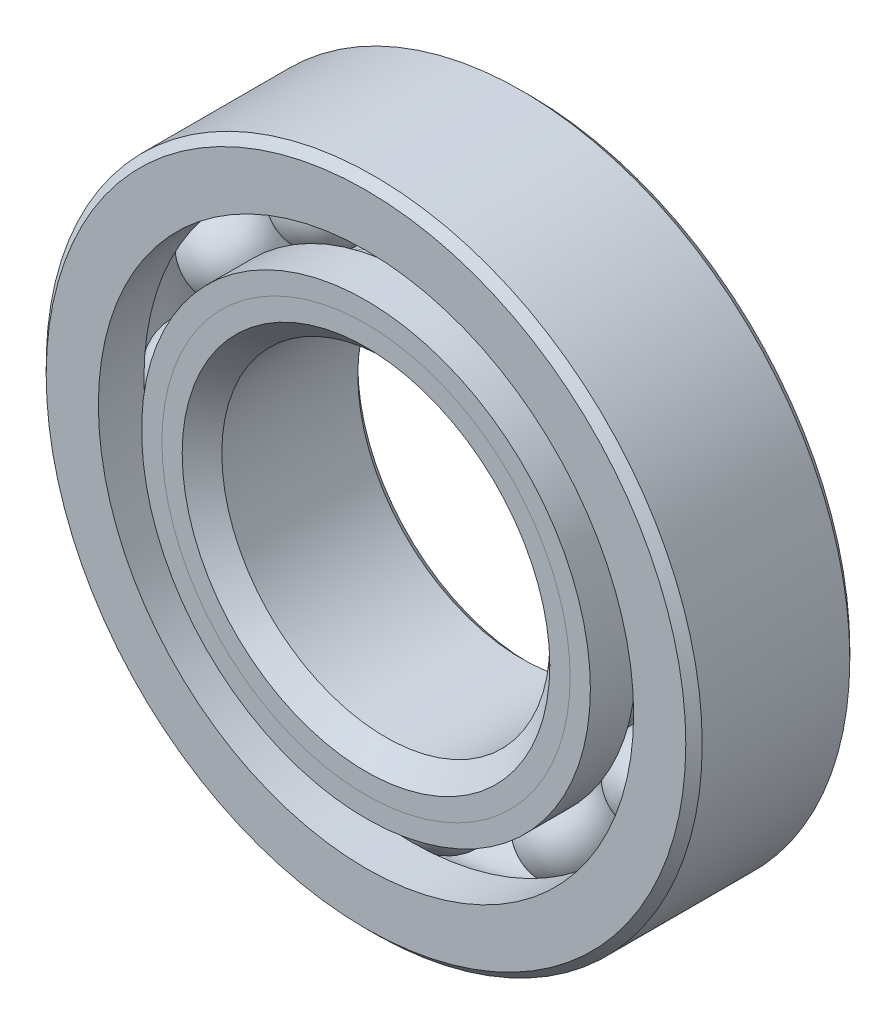
SolidWorks part; units mm, degrees
ref_plane "Front Plane" through (0, 0, 0) normal (0, 0, 1) x (1, 0, 0)
ref_plane "Top Plane" through (0, 0, 0) normal (0, 1, 0) x (1, 0, 0)
ref_plane "Right Plane" through (0, 0, 0) normal (1, 0, 0) x (0, 0, -1)
sketch "Sketch1" plane through (0, 0, 0) normal (1, 0, 0) x (0, 0, -1)
  line L0 (-1.5875, 0) -> (1.5875, 0) construction
  line L1 (0, 6.35) -> (0, -6.35) construction
  line L2 (1.4288, 6.35) -> (-1.4288, 6.35)
  line L3 (-1.4288, 6.35) -> (-1.5875, 6.1913)
  line L4 (-1.5875, 6.1913) -> (-1.5875, 5.1812)
  line L5 (-1.5875, 5.1812) -> (-0.7056, 5.1812)
  line L6 (1.5875, 5.1812) -> (0.7056, 5.1812)
  line L7 (1.5875, 6.1913) -> (1.5875, 5.1812)
  line L8 (1.4288, 6.35) -> (1.5875, 6.1913)
  line L9 (0, 6.35) -> (0, 4.7625) construction
  line L10 (0, 4.7625) -> (0, 3.175) construction
  arc A0 (-0.7056, 5.1812) -> (0.7056, 5.1812) centre (0, 4.7625) cw
  point P14 (0, 3.175)
  dimension "Width" = 3.175
  dimension "OD" = 12.7
  dimension "D1" = 45
  dimension "D2" = 0.1588
  dimension "D3" = 1.4111
  dimension "D4" = 0.4187
revolve "Revolve1" add sketch "Sketch1" angle 360 about L0
sketch "Sketch2" plane through (0, 0, 0) normal (1, 0, 0) x (0, 0, -1)
  line L0 (-1.5875, 4.3438) -> (-0.7056, 4.3438)
  line L1 (-1.5875, 6.1913) -> (-1.5875, -6.1913) construction
  line L2 (-1.5875, 4.3438) -> (-1.5875, 3.9512)
  line L3 (-1.5875, 3.9512) -> (-1.1949, 3.5585)
  line L4 (-1.1949, 3.5585) -> (0, 3.5585)
  line L5 (0, 6.35) -> (0, -6.35) construction
  line L6 (0, 3.5585) -> (0, 3.9421)
  line L7 (0, 3.9421) -> (0, 3.175) construction
  line L8 (-1.5875, 4.3438) -> (-1.5875, 3.5585) construction
  line L9 (-1.5875, 3.5585) -> (-1.1949, 3.5585) construction
  arc A0 (-0.7056, 4.3438) -> (0, 3.9421) centre (0, 4.7625) ccw
  arc A1 (0.7056, 5.1812) -> (-0.7056, 5.1812) centre (0, 4.7625) ccw construction
  circle A2 centre (0, 4.7625) radius 0.8204 construction
  dimension "D1" = 45
revolve "Revolve2" add sketch "Sketch2" angle 360 about L0
sketch "Sketch3" plane through (0, 0, 0) normal (1, 0, 0) x (0, 0, -1)
  line L0 (-1.5875, 3.9512) -> (-1.1949, 3.5585)
  line L1 (-1.1949, 3.5585) -> (0, 3.5585)
  line L2 (0, 3.5585) -> (0, 3.9421)
  line L3 (-1.5875, 3.9512) -> (-1.5875, 3.5585)
  line L4 (-1.5875, 4.3438) -> (-1.5875, 3.5585) construction
  line L5 (-1.5875, 3.5585) -> (-1.204, 3.175)
  line L6 (-1.204, 3.175) -> (1.4288, 3.175)
  line L7 (1.4288, 6.35) -> (1.4288, -6.35) construction
  line L8 (1.4288, 3.175) -> (1.5875, 3.3337)
  line L9 (1.5875, -6.1913) -> (1.5875, 6.1913) construction
  line L10 (1.5875, 3.3337) -> (1.5875, 4.3438)
  line L11 (1.5875, 4.3438) -> (0.7056, 4.3438)
  line L13 (1.4288, 6.35) -> (1.5875, 6.1913) construction
  circle A0 centre (0, 4.7625) radius 0.8204 construction
  arc A1 (0.7056, 4.3438) -> (0, 3.9421) centre (0, 4.7625) cw
revolve "Revolve3" add sketch "Sketch3" angle 360 about L0
sketch "Sketch4" plane through (0, 0, 0) normal (1, 0, 0) x (0, 0, -1)
  line L0 (-0.8204, 4.7625) -> (0.8204, 4.7625)
  circle A1 centre (0, 4.7625) radius 0.8204 construction
  arc A2 (-0.8204, 4.7625) -> (0.8204, 4.7625) centre (0, 4.7625) cw
  arc A3 (0.7056, 5.1812) -> (-0.7056, 5.1812) centre (0, 4.7625) ccw construction
revolve "Revolve4" add sketch "Sketch4" angle 360 about L0
ref_axis "Axis1" through (0, 0, -1.5875) along (0, 0, 1)
pattern_circular "CirPattern1" count 12 every 30 about axis through (0, 0, -1.5875) along (0, 0, 1) of bodies 104
equation "\"D2@Sketch1\" = \"Width@Sketch1\"*.05"
equation "\"D3@Sketch1\" = \"Width@Sketch1\"/2.25"
equation "\"D4@Sketch1\" = (((\"OD@Sketch1\"-\"Width@Sketch1\")/2)/3.25)/3.5"
equation "\"D2@CirPattern1\" = 360/\"Balls@CirPattern1\""
